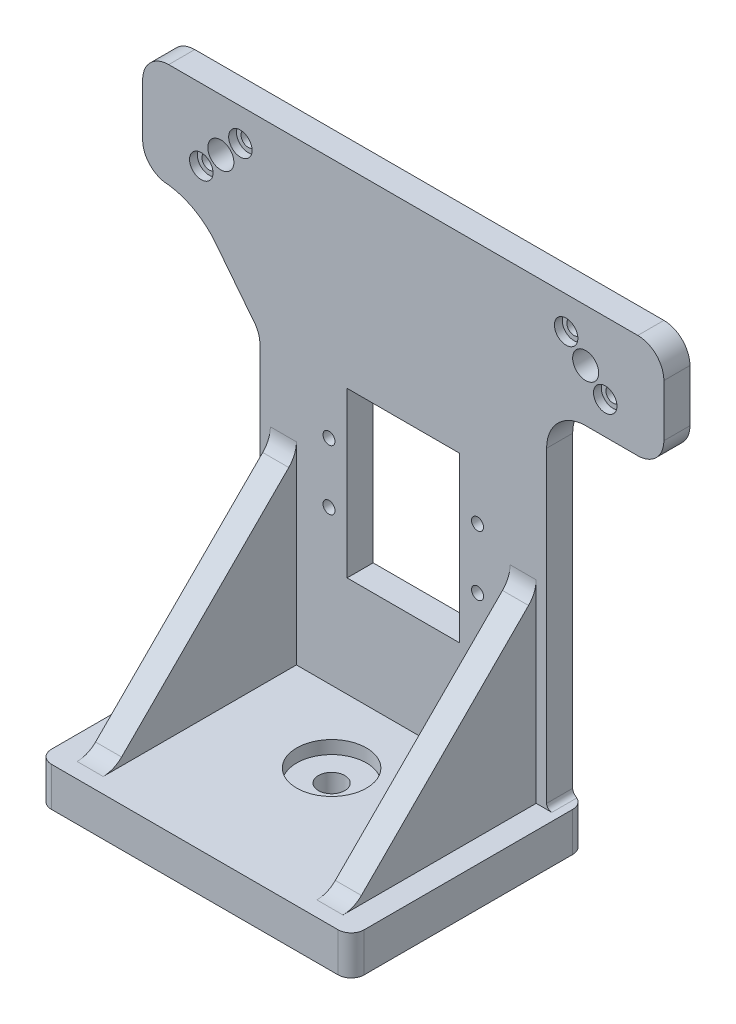
SolidWorks part; units mm, degrees
ref_plane "Ebene vorne" through (0, 0, 0) normal (0, 0, 1) x (1, 0, 0)
ref_plane "Ebene oben" through (0, 0, 0) normal (0, 1, 0) x (1, 0, 0)
ref_plane "Ebene rechts" through (0, 0, 0) normal (1, 0, 0) x (0, 0, -1)
sketch "Skizze1" plane through (0, 0, 0) normal (0, 0, 1) x (1, 0, 0)
  line L0 (0, 0) -> (0, 120.8446) construction
  line L1 (0, 120.8446) -> (0, -115.4537) construction
  line L2 (-21.55, 2.2046) -> (-75.2531, 2.2046) construction
  line L15 (90, 107.0546) -> (-90, 107.0546)
  line L16 (-100, 97.0546) -> (-100, 77.0546)
  line L17 (-90, 67.0546) -> (-70, 67.0546)
  line L18 (-55, 52.0546) -> (-55, -67.9454)
  line L19 (-55, -67.9454) -> (-60, -67.9454)
  line L20 (-60, -67.9454) -> (-60, -82.9454)
  line L21 (-60, -82.9454) -> (60, -82.9454)
  line L22 (60, -67.9454) -> (60, -82.9454)
  line L23 (55, -67.9454) -> (60, -67.9454)
  line L24 (55, 52.0546) -> (55, -67.9454)
  line L25 (90, 67.0546) -> (70, 67.0546)
  line L26 (100, 97.0546) -> (100, 77.0546)
  line L27 (21.55, 33.7046) -> (-21.55, 33.7046)
  line L28 (-21.55, 33.7046) -> (-21.55, -29.2954)
  line L29 (-21.55, -29.2954) -> (21.55, -29.2954)
  line L30 (-28.5, 26.717) -> (-28.5, -23.7709) construction
  line L31 (21.55, 33.7046) -> (21.55, -29.2954)
  line L32 (-152.8572, 87.0546) -> (12.8572, 87.0546) construction
  line L33 (-62.5, 94.5546) -> (-83.4096, 94.5546) construction
  line L34 (-77.5, 79.5546) -> (-83.4096, 79.5546) construction
  line L35 (-62.5, 94.5546) -> (-62.5, 69.0538) construction
  line L36 (-77.5, 79.5546) -> (-77.5, 100.8525) construction
  line L37 (-21.55, 2.2046) -> (21.55, 2.2046) construction
  line L38 (-55, -67.9454) -> (55, -67.9454) construction
  arc A0 (-100, 77.0546) -> (-90, 67.0546) centre (-90, 77.0546) ccw
  arc A1 (-90, 107.0546) -> (-100, 97.0546) centre (-90, 97.0546) ccw
  arc A2 (-70, 67.0546) -> (-55, 52.0546) centre (-70, 52.0546) cw
  arc A3 (70, 67.0546) -> (55, 52.0546) centre (70, 52.0546) ccw
  arc A4 (90, 107.0546) -> (100, 97.0546) centre (90, 97.0546) cw
  arc A5 (100, 77.0546) -> (90, 67.0546) centre (90, 77.0546) cw
  circle A6 centre (-28.5, 13.7046) radius 2.3
  circle A7 centre (-28.5, -9.2954) radius 2.3
  circle A8 centre (28.5, -9.2954) radius 2.3
  circle A9 centre (28.5, 13.7046) radius 2.3
  circle A10 centre (-70, 87.0546) radius 5
  circle A11 centre (-62.5, 94.5546) radius 2.75
  circle A12 centre (-77.5, 79.5546) radius 2.75
  circle A13 centre (77.5, 79.5546) radius 2.75
  circle A14 centre (62.5, 94.5546) radius 2.75
  circle A15 centre (70, 87.0546) radius 5
  point P18 (-100, 107.0546)
  point P22 (0, 107.0546)
  point P23 (0, -82.9454)
  point P33 (100, 107.0546)
  point P50 (0, -29.2954)
  point P51 (0, 33.7046)
  dimension "D7" = 10
  dimension "D8" = 15
  dimension "D11" = 4.6
  dimension "D12" = 4.6
  dimension "D15" = 10
  dimension "D16" = 5.5
  dimension "D17" = 5.5
  dimension "D1" = 100
  dimension "D2" = 55
  dimension "D3" = 60
  dimension "D4" = 40
  dimension "D5" = 135
  dimension "D6" = 15
  dimension "D9" = 63
  dimension "D10" = 21.55
  dimension "D13" = 28.5
  dimension "D14" = 23
  dimension "D18" = 7.5
  dimension "D19" = 7.5
  dimension "D20" = 7.5
  dimension "D21" = 7.5
  dimension "D22" = 20
  dimension "D23" = 140
  dimension "D24" = 84.85
extrude "Aufsatz-Linear austragen1" add sketch "Skizze1" along normal blind 10
sketch "Skizze2" plane through (0, 0, 10) normal (0, 0, 1) x (1, 0, 0)
  line L0 (-21.55, 2.2046) -> (21.55, 2.2046) construction
  line L1 (-21.55, 33.7046) -> (-21.55, -29.2954) construction
  line L2 (21.55, -29.2954) -> (21.55, 33.7046) construction
  line L3 (0, 33.7046) -> (0, -29.2954) construction
  line L4 (21.55, 33.7046) -> (-21.55, 33.7046) construction
  line L5 (-21.55, -29.2954) -> (21.55, -29.2954) construction
  line L6 (-70, 92.0546) -> (-70, 82.0546) construction
  line L7 (-65, 87.0546) -> (-75, 87.0546) construction
  line L8 (-13.4991, -8.9319) -> (-83.4991, 75.9181)
  line L9 (-56.5009, 98.1912) -> (13.4991, 13.3412)
  circle A0 centre (-70, 87.0546) radius 5 construction
  circle A1 centre (0, 2.2046) radius 17.5
  circle A2 centre (-70, 87.0546) radius 17.5
  dimension "D1" = 35
  dimension "D2" = 35
sketch "Skizze3" plane through (0, 0, 10) normal (0, 0, 1) x (1, 0, 0)
  line L0 (-90, 67.0546) -> (-70, 67.0546) construction
  line L1 (-72.8459, 57.8146) -> (-56.7743, 37.3523)
  line L2 (-55, 52.0546) -> (-55, -67.9454) construction
  line L3 (-55, 18.961) -> (-43.3334, 21.2005)
  line L4 (-43.3334, 21.2005) -> (-45.498, 67.0546)
  line L5 (-45.498, 67.0546) -> (-90, 67.0546)
  arc A0 (-100, 77.0546) -> (-90, 67.0546) centre (-90, 77.0546) ccw construction
  spline S0 degree 2 poles (-90, 67.0546) (-79.9383, 65.6564) (-72.8459, 57.8146) knots 0 0 0 1 1 1
  spline S1 degree 2 poles (-55, 18.961) (-46.6365, 27.9631) (-56.7743, 37.3523) knots 0 0 0 1 1 1
extrude "Aufsatz-Linear austragen3" add sketch "Skizze3" against normal blind 10
sketch "Skizze4" plane through (0, 0, 10) normal (0, 0, 1) x (1, 0, 0)
  line L1 (-60, -67.9454) -> (60, -67.9454)
  line L2 (-60, -67.9454) -> (-60, -82.9454)
  line L3 (-60, -82.9454) -> (60, -82.9454)
  line L4 (60, -67.9454) -> (60, -82.9454)
extrude "Aufsatz-Linear austragen4" add sketch "Skizze4" along normal blind 80
sketch "Skizze6" plane through (-55, 0, 0) normal (-1, 0, 0) x (0, 0, 1)
  line L5 (60.1366, -67.0551) -> (60.1366, -66.9447)
ref_plane "Ebene1" through (-51, 0, 0) normal (-1, 0, 0) x (0, 0, 1)
sketch "Skizze9" plane through (-51, 0, 0) normal (-1, 0, 0) x (0, 0, 1)
  line L0 (10, 2.0546) -> (80, -67.9454)
  line L1 (10, 35.555) -> (10, -67.9454) construction
  line L2 (90, -67.9454) -> (0, -67.9454) construction
  line L3 (80, -67.9454) -> (6.6442, -67.9454)
  line L4 (10, -67.9454) -> (0, -67.9454) construction
  line L5 (6.6442, -67.9454) -> (6.6442, 2.0546)
  line L6 (6.6442, 2.0546) -> (10, 2.0546)
  dimension "D1" = 70
  dimension "D2" = 70
extrude "Aufsatz-Linear austragen5" add sketch "Skizze9" against normal blind 10
ref_plane "Ebene2" through (51, 0, 0) normal (1, 0, 0) x (0, 0, -1)
sketch "Skizze10" plane through (51, 0, 0) normal (1, 0, 0) x (0, 0, -1)
  line L0 (-10, 2.2046) -> (-80, -67.9454)
  line L1 (-10, 19.7046) -> (-10, -15.2954) construction
  line L2 (-80, -67.9454) -> (-10, -67.9454)
  line L3 (-90, -67.9454) -> (0, -67.9454) construction
  line L4 (-80, -67.9454) -> (-10, -67.9454) construction
  line L5 (-10, -67.9454) -> (-10, 2.2046)
extrude "Aufsatz-Linear austragen6" add sketch "Skizze10" against normal blind 10
fillet "Verrundung3" radius 10 4 edges at (-46, -67.9454, 80) (46, -67.9454, 80) (46, 2.2046, 10) (-46, 2.0546, 10)
fillet "Verrundung4" radius 5 4 edges at (-60, -75.4454, 90) (60, -75.4454, 90) (60, -75.4454, 0) (-60, -75.4454, 0)
fillet "Verrundung5" radius 10 1 edges at (-55, 35.555, 5)
sketch "Skizze11" plane through (0, 0, 10) normal (0, 0, 1) x (1, 0, 0)
  circle A0 centre (62.5, 94.5546) radius 4.5
  circle A2 centre (77.5, 79.5546) radius 4.5
  circle A3 centre (-62.5, 94.5546) radius 4.5
  circle A4 centre (-77.5, 79.5546) radius 4.5
  dimension "D1" = 9
  dimension "D2" = 9
  dimension "D3" = 9
  dimension "D4" = 9
extrude "Schnitt-Linear austragen1" cut sketch "Skizze11" against normal blind 3
sketch "Skizze12" plane through (0, 0, 0) normal (0, 0, -1) x (-1, 0, 0)
  line L0 (26.2, 13.7046) -> (30.8, 13.7046) construction
  line L1 (28.5, 16.0046) -> (28.5, 11.4046) construction
  line L2 (28.5, 16.0046) -> (28.5, 17.7471) construction
  line L3 (28.5, 11.4046) -> (28.5, 9.6621) construction
  line L4 (28.5, 17.7471) -> (24.825, 15.7871)
  line L5 (24.825, 15.7871) -> (24.825, 11.6221)
  line L6 (24.825, 11.6221) -> (28.5, 9.6621)
  line L7 (32.175, 11.6221) -> (28.5, 9.6621)
  line L8 (32.175, 15.7871) -> (32.175, 11.6221)
  line L9 (28.5, 17.7471) -> (32.175, 15.7871)
  line L10 (26.2, -9.2954) -> (30.8, -9.2954) construction
  line L11 (28.5, -6.9954) -> (28.5, -11.5954) construction
  line L12 (28.5, -6.9954) -> (28.5, -5.2529) construction
  line L13 (28.5, -11.5954) -> (28.5, -13.3379) construction
  line L14 (28.5, -5.2529) -> (24.825, -7.2129)
  line L15 (24.825, -7.2129) -> (24.825, -11.3779)
  line L16 (24.825, -11.3779) -> (28.5, -13.3379)
  line L17 (32.175, -11.3779) -> (28.5, -13.3379)
  line L18 (32.175, -7.2129) -> (32.175, -11.3779)
  line L19 (28.5, -5.2529) -> (32.175, -7.2129)
  line L20 (-30.8, -9.2954) -> (-26.2, -9.2954) construction
  line L21 (-28.5, -6.9954) -> (-28.5, -11.5954) construction
  line L22 (-28.5, -6.9954) -> (-28.5, -5.2529) construction
  line L23 (-28.5, -11.5954) -> (-28.5, -13.3379) construction
  line L24 (-28.5, -5.2529) -> (-32.175, -7.2129)
  line L25 (-32.175, -7.2129) -> (-32.175, -11.3779)
  line L26 (-32.175, -11.3779) -> (-28.5, -13.3379)
  line L27 (-24.825, -11.3779) -> (-28.5, -13.3379)
  line L28 (-24.825, -7.2129) -> (-24.825, -11.3779)
  line L29 (-28.5, -5.2529) -> (-24.825, -7.2129)
  line L30 (-30.8, 13.7046) -> (-26.2, 13.7046) construction
  line L31 (-28.5, 16.0046) -> (-28.5, 11.4046) construction
  line L32 (-28.5, 16.0046) -> (-28.5, 17.7471) construction
  line L33 (-28.5, 11.4046) -> (-28.5, 9.6621) construction
  line L34 (-28.5, 17.7471) -> (-32.175, 15.7871)
  line L35 (-32.175, 15.7871) -> (-32.175, 11.6221)
  line L36 (-32.175, 11.6221) -> (-28.5, 9.6621)
  line L37 (-24.825, 11.6221) -> (-28.5, 9.6621)
  line L38 (-24.825, 15.7871) -> (-24.825, 11.6221)
  line L39 (-28.5, 17.7471) -> (-24.825, 15.7871)
  circle A0 centre (28.5, 13.7046) radius 2.3 construction
  circle A1 centre (28.5, -9.2954) radius 2.3 construction
  circle A2 centre (-28.5, -9.2954) radius 2.3 construction
  circle A3 centre (-28.5, 13.7046) radius 2.3 construction
  dimension "D1" = 8.085
  dimension "D2" = 3.675
  dimension "D3" = 8.085
  dimension "D4" = 3.675
  dimension "D5" = 8.085
  dimension "D6" = 3.675
  dimension "D7" = 8.085
  dimension "D8" = 3.675
extrude "Schnitt-Linear austragen2" cut sketch "Skizze12" against normal blind 3
fillet "Verrundung6" radius 2 2 edges at (55, -67.9454, 5) (-55, -67.9454, 5)
sketch "Skizze13" plane through (0, -67.9454, 0) normal (0, 1, 0) x (1, 0, 0)
  line L0 (-17.5, -10) -> (17.5, -10) construction
  line L1 (0, 0) -> (0, -90) construction
  line L2 (55, -90) -> (-55, -90) construction
  circle A0 centre (0, -37.5) radius 5.05
  dimension "D1" = 10.1
  dimension "D2" = 27.5
extrude "Schnitt-Linear austragen3" cut sketch "Skizze13" against normal through all
sketch "Skizze14" plane through (0, -67.9454, 0) normal (0, 1, 0) x (1, 0, 0)
  circle A0 centre (0, -37.5) radius 13.3825
  dimension "D1" = 26.765
extrude "Schnitt-Linear austragen4" cut sketch "Skizze14" against normal blind 5 contours A0
equation "\"D10@Skizze1\"=43.1/2"
equation "\"D13@Skizze1\"=57/2"
equation "\"D1@Skizze13\"=10*1.01"
